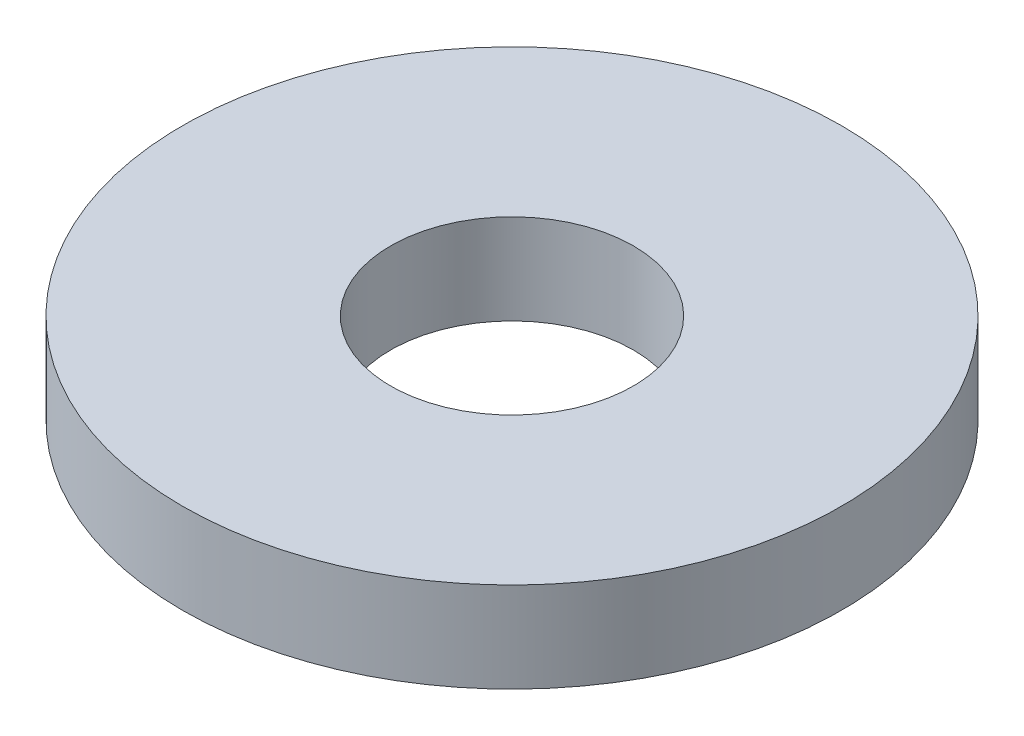
SolidWorks part; units mm, degrees
ref_plane "Front Plane" through (0, 0, 0) normal (0, 0, 1) x (1, 0, 0)
ref_plane "Top Plane" through (0, 0, 0) normal (0, 1, 0) x (1, 0, 0)
ref_plane "Right Plane" through (0, 0, 0) normal (1, 0, 0) x (0, 0, -1)
sketch "Sketch1" plane through (0, 0, 0) normal (0, 1, 0) x (1, 0, 0)
  circle A0 centre (0, 0) radius 95
  dimension "FLANGE_OD" = 190
extrude "Boss-Extrude1" add sketch "Sketch1" along normal blind 26
sketch "Sketch2" plane through (0, 0, 0) normal (0, 1, 0) x (1, 0, 0)
  circle A0 centre (0, 0) radius 35
  dimension "BORE_D" = 70
extrude "Cut-Extrude1" cut sketch "Sketch2" along normal through all
sketch "Sketch3" plane through (0, 26, 0) normal (0, 1, 0) x (1, 0, 0)
  circle A0 centre (0, 0) radius 30.1862 construction
  circle A1 centre (-30.1862, 0) radius 3.3949
  dimension "BOLT_D" = 6.7898
  dimension "BOLT_PCD" = 60.3724
extrude "Cut-Extrude2" cut sketch "Sketch3" against normal blind 25.1671 rebuild error yes
pattern_circular "CirPattern1" count 3 over 360 rebuild error yes
